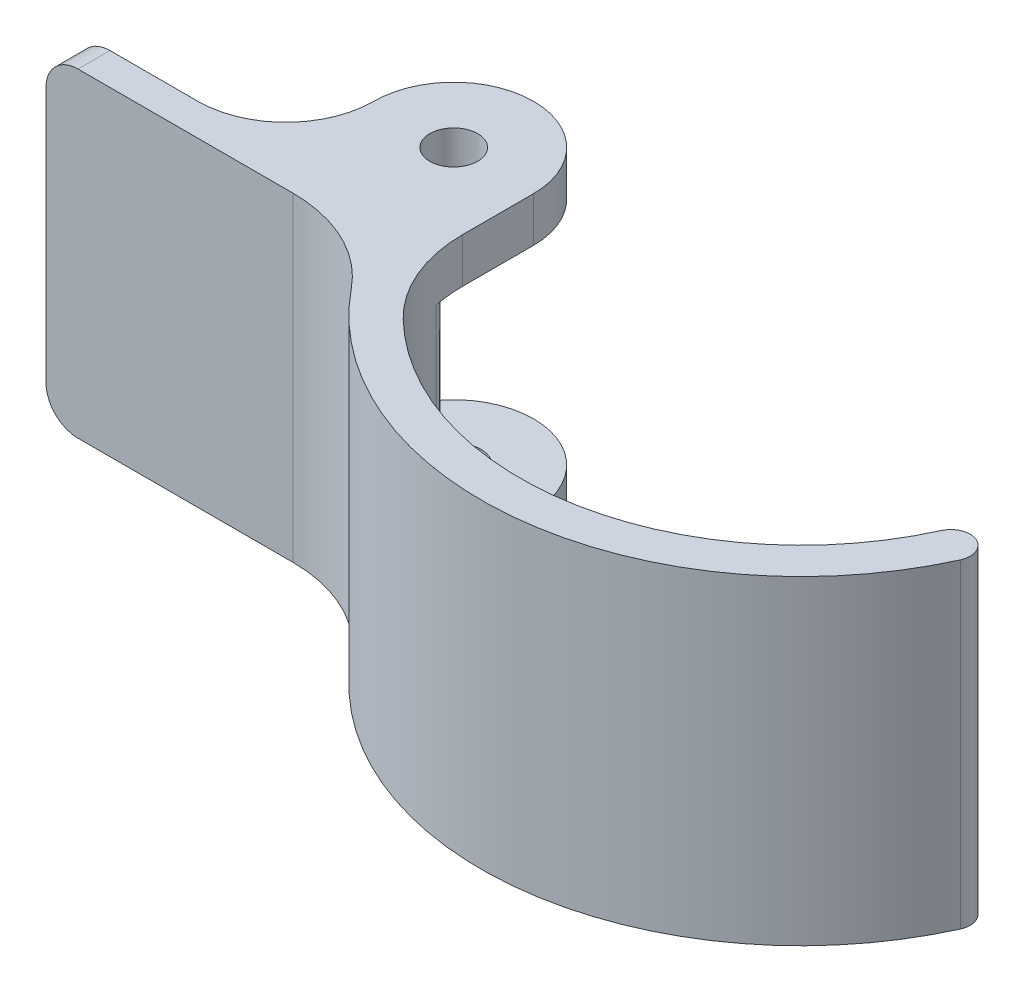
SolidWorks part; units mm, degrees
ref_plane "Front Plane" through (0, 0, 0) normal (0, 0, 1) x (1, 0, 0)
ref_plane "Top Plane" through (0, 0, 0) normal (0, 1, 0) x (1, 0, 0)
ref_plane "Right Plane" through (0, 0, 0) normal (1, 0, 0) x (0, 0, -1)
sketch "Sketch1" plane through (0, 0, 0) normal (0, 0, 1) x (1, 0, 0)
  line L0 (0, 10) -> (0, -10) construction
  line L1 (-12, -10) -> (5, -10)
  line L2 (-12, -10) -> (-12, 10)
  line L3 (-12, 10) -> (5, 10)
  line L4 (5, -10) -> (5, 10)
  dimension "D1" = 20
  dimension "D2" = 12
  dimension "D3" = 5
extrude "Boss-Extrude1" add sketch "Sketch1" along normal blind 2
sketch "Sketch2" plane through (0, 10, 0) normal (0, 1, 0) x (1, 0, 0)
  line L0 (0, 0) -> (0, 5.5) construction
  line L1 (5, 0) -> (-5, 0)
  line L2 (5, 0) -> (-12, 0) construction
  line L3 (-5, 0) -> (-5, 5.5)
  line L4 (5, 0) -> (5, 5.5)
  line L5 (-5, 5.5) -> (5, 5.5) construction
  circle A0 centre (0, 5.5) radius 1.5
  arc A1 (-5, 5.5) -> (5, 5.5) centre (0, 5.5) cw
  dimension "D1" = 3
  dimension "D2" = 5
  dimension "D3" = 5.5
extrude "Boss-Extrude2" add sketch "Sketch2" against normal blind 2.8
fillet "Fillet1" radius 5.5 1 edges at (-5, 8.6, 0)
mirror "Mirror1" about plane through (0, 0, 0) normal (0, 1, 0) of "Fillet1", "Boss-Extrude2"
hole_wizard "CSK for M3 Countersunk Flat Head Screw1" positions "Sketch3" profile "Sketch4" countersink size "M3" standard "DIN"
sketch "Sketch3" plane through (0, -10, 0) normal (0, -1, 0) x (-1, 0, 0)
  point P0 (0, 5.5)
sketch "Sketch4" plane through (0, -10, -5.5) normal (1, 0, 0) x (0, 0, -1)
  line L0 (0, 0) -> (0, 8.0215)
  line L1 (0, 8.0215) -> (1.7, 7)
  line L2 (1.7, 7) -> (1.7, 1.45)
  line L3 (1.7, 1.45) -> (3.15, 0)
  line L5 (3.15, 0) -> (0, 0)
  line L6 (-1.7, 1.45) -> (-3.15, 0) construction
  line L10 (0, 8.0215) -> (-1.7, 7) construction
  line L11 (0, -6.35) -> (0, 107.95) construction
  dimension "Hole Dia." = 3.4
  dimension "Hole Depth" = 7
  dimension "Near C'Sink Dia." = 6.3
  dimension "Near C'Sink Angle" = 90
  dimension "Drill Angle" = 118
sketch "Sketch5" plane through (0, 0, 2) normal (0, 0, 1) x (1, 0, 0)
  line L0 (0, 0) -> (-18, 0) construction
  line L1 (-12, 10) -> (-12, -10)
  line L2 (5, 10) -> (-12, 10) construction
  line L3 (-12, -10) -> (5, -10) construction
  line L4 (-12, 10) -> (-12, -10) construction
  line L5 (-18, -10) -> (-18, 10)
  line L6 (-18, 10) -> (-12, 10)
  line L7 (-18, -10) -> (-12, -10)
  dimension "D1" = 18
extrude "Boss-Extrude3" add sketch "Sketch5" against normal up to surface (2 mm away) up to face at (-7, 0, 0)
fillet "Fillet2" radius 2 2 edges at (-18, -10, 1) (-18, 10, 1)
sketch "Sketch6" plane through (0, 10, 0) normal (0, 1, 0) x (1, 0, 0)
  line L0 (0, 0) -> (36, 0) construction
  line L2 (2.2399, -2) -> (4.3672, -0.8888)
  line L3 (5, -2) -> (-16, -2) construction
  arc A0 (4.3672, -0.8888) -> (17.5794, -10.1774) centre (19.9671, 7.2599) ccw construction
  arc A1 (2.2399, -2) -> (38.1863, -0.99) centre (19.9671, 7.2599) ccw
  arc A2 (4.3672, -0.8888) -> (36, 0) centre (19.9671, 7.2599) ccw
  arc A3 (2.2399, -2) -> (17.2538, -12.5552) centre (19.9671, 7.2599) ccw construction
  arc A4 (36, 0) -> (38.1863, -0.99) centre (37.0932, -0.495) cw
  dimension "D2" = 2.4
  dimension "D3" = 20
  dimension "D4" = 36
extrude "Boss-Extrude4" add sketch "Sketch6" against normal up to surface (20 mm away) up to face at (0, -10, -8.65)
fillet "Fillet3" radius 9 1 edges at (5, 0, 2)
fillet "Fillet4" radius 9 1 edges at (2.2399, 0, 2)
fillet "Fillet5" radius 1 1 edges at (5.0635, 0, 0)
